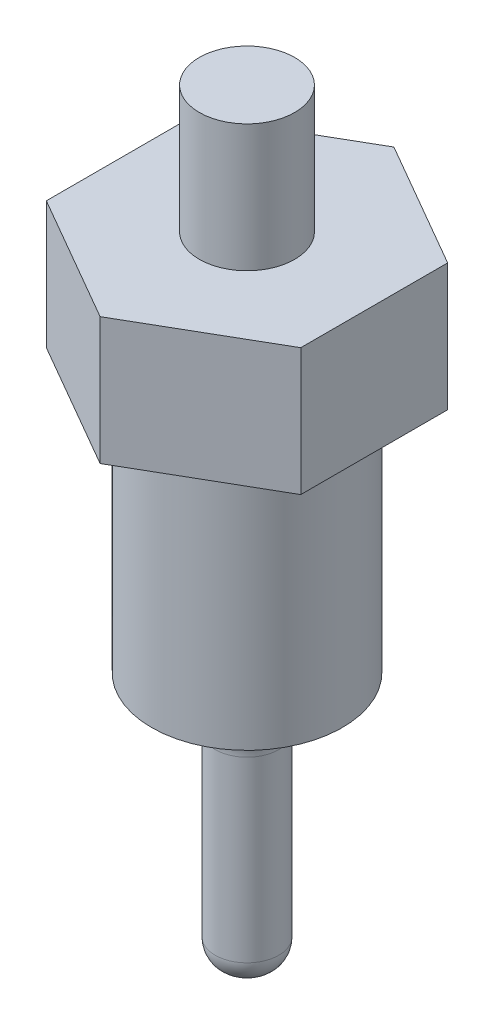
SolidWorks part; units mm, degrees
material "AISI 304"
ref_plane "Front Plane" through (0, 0, 0) normal (0, 0, 1) x (1, 0, 0)
ref_plane "Top Plane" through (0, 0, 0) normal (0, 1, 0) x (1, 0, 0)
ref_plane "Right Plane" through (0, 0, 0) normal (1, 0, 0) x (0, 0, -1)
sketch "Sketch1" plane through (0, 0, 0) normal (0, 0, 1) x (1, 0, 0)
  line L0 (0, 0) -> (0, 38.1)
  line L1 (0, 38.1) -> (2.3812, 38.1)
  line L2 (2.3812, 38.1) -> (2.3812, 31.75)
  line L3 (2.3812, 31.75) -> (12.7, 31.75)
  line L4 (12.7, 31.75) -> (12.7, 25.4)
  line L5 (12.7, 25.4) -> (4.7625, 25.4)
  line L6 (4.7625, 25.4) -> (4.7625, 12.7)
  line L7 (4.7625, 12.7) -> (1.5875, 12.7)
  line L8 (1.5875, 12.7) -> (1.5875, 0)
  line L9 (1.5875, 0) -> (0, 0)
  line L10 (0, 0) -> (0, -5.7178) construction
  point P12 (4.7625, 27.1479)
  point P13 (12.7, 22.86)
  dimension "D1" = 3.175
  dimension "D2" = 9.525
  dimension "D3" = 25.4
  dimension "D4" = 12.7
  dimension "D5" = 12.7
  dimension "D6" = 6.35
  dimension "D7" = 6.35
  dimension "D8" = 4.7625
revolve "Revolve1" add sketch "Sketch1" angle 360 about L10
sketch "Sketch2" plane through (0, 0, 0) normal (0, 1, 0) x (1, 0, 0)
  line L1 (6.35, 3.6662) -> (0, 7.3323)
  line L2 (0, 7.3323) -> (-6.35, 3.6662)
  line L3 (-6.35, 3.6662) -> (-6.35, -3.6662)
  line L4 (-6.35, -3.6662) -> (0, -7.3323)
  line L5 (0, -7.3323) -> (6.35, -3.6662)
  line L6 (6.35, -3.6662) -> (6.35, 3.6662)
  circle A0 centre (0, 0) radius 6.35 construction
  point P1 (8.9271, 5.1541)
  dimension "D1" = 12.7
extrude "Cut-Extrude1" cut sketch "Sketch2" along normal through all flip side to cut
fillet "Fillet1" radius 2.54 1 edges at (0, 12.7, 1.5875)
fillet "Fillet2" radius 1.27 1 edges at (0, 0, 1.5875)
